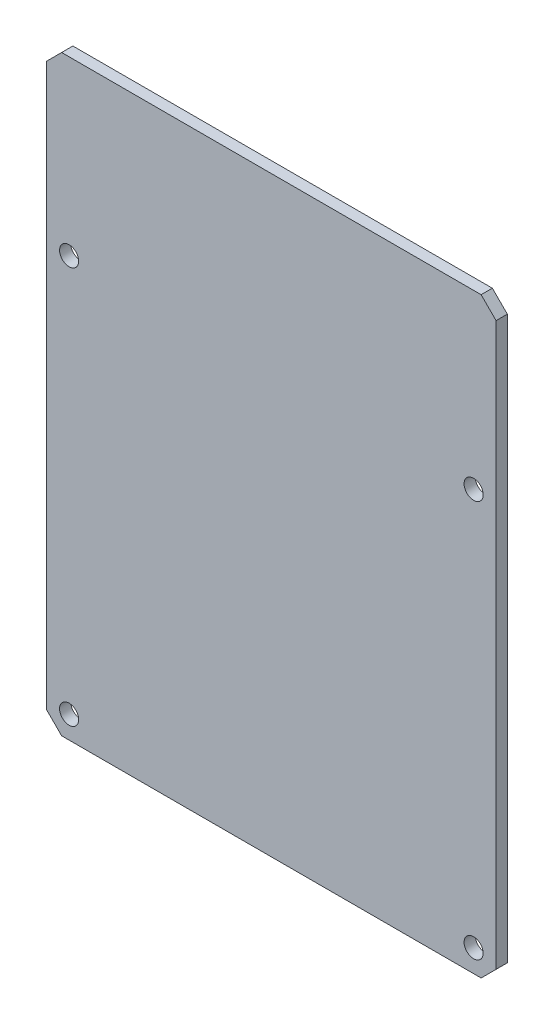
SolidWorks part; units mm, degrees
material "Плата обработки данных, сложная"
ref_plane "Спереди" through (0, 0, 0) normal (0, 0, 1) x (1, 0, 0)
ref_plane "Сверху" through (0, 0, 0) normal (0, 1, 0) x (1, 0, 0)
ref_plane "Справа" through (0, 0, 0) normal (1, 0, 0) x (0, 0, -1)
sketch "Эскиз1" plane through (0, 0, 0) normal (0, 0, 1) x (1, 0, 0)
  line L1 (-30, -39.5) -> (30, -39.5)
  line L2 (-30, -39.5) -> (-30, 39.5)
  line L3 (-30, 39.5) -> (30, 39.5)
  line L4 (30, -39.5) -> (30, 39.5)
  line L5 (-30, -39.5) -> (30, 39.5) construction
  line L6 (-30, 39.5) -> (30, -39.5) construction
  point P0 (0, 0)
  dimension "D1" = 60
  dimension "D2" = 79
extrude "Бобышка-Вытянуть1" add sketch "Эскиз1" along normal blind 1.5
chamfer "Фаска1" distance 2 angle 45 4 edges at (-30, -39.5, 0.75) (-30, 39.5, 0.75) (30, -39.5, 0.75) (30, 39.5, 0.75)
sketch "Эскиз2" plane through (0, 0, 1.5) normal (0, 0, 1) x (1, 0, 0)
  line L0 (-30, 37.5) -> (-30, -37.5) construction
  line L1 (-28, -39.5) -> (28, -39.5) construction
  point P0 (-27, 16.5)
  point P1 (27, 16.5)
  point P2 (27, -36.5)
  point P3 (-27, -36.5)
  dimension "D1" = 54
  dimension "D2" = 53
  dimension "D3" = 3
  dimension "D4" = 3
hole_wizard "Сверло под метчик  спиральное M2.51" positions "Эскиз3" profile "Эскиз4" hole size "M2.5x0.45" standard "DIN" end condition through all
sketch "Эскиз3" plane through (0, 0, 1.5) normal (0, 0, 1) x (1, 0, 0)
  point P0 (-27, 16.5)
  point P3 (27, 16.5)
  point P6 (27, -36.5)
  point P9 (-27, -36.5)
sketch "Эскиз4" plane through (-27, 16.5, 1.5) normal (1, 0, 0) x (0, -1, 0)
  line L0 (0, 0) -> (0, 1.5)
  line L1 (0, 1.5) -> (1.275, 1.5)
  line L2 (1.275, 1.5) -> (1.275, 0)
  line L5 (1.275, 0) -> (0, 0)
  line L11 (0, -6.35) -> (0, 107.95) construction
  dimension "Диаметр сквозного отверстия" = 2.55
  dimension "Глубина сквозного отверстия" = 1.5
